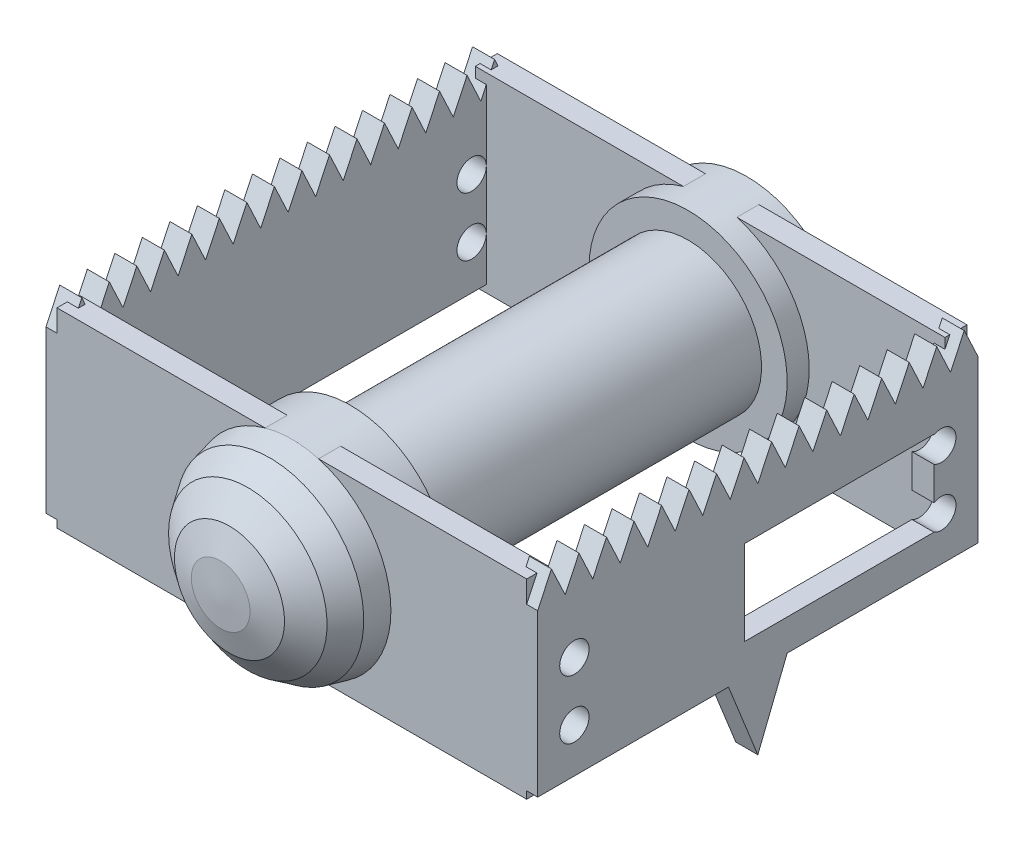
SolidWorks part; units mm, degrees
ref_plane "Alzado" through (0, 0, 0) normal (0, 0, 1) x (1, 0, 0)
ref_plane "Planta" through (0, 0, 0) normal (0, 1, 0) x (1, 0, 0)
ref_plane "Vista lateral" through (0, 0, 0) normal (1, 0, 0) x (0, 0, -1)
sketch "Sk_Eje_cuerpo" plane through (0, 0, 0) normal (0, 1, 0) x (1, 0, 0)
  line L0 (183.5, -84) -> (186, -84)
  line L1 (186, -84) -> (186, -92)
  line L2 (186, -92) -> (182.5, -92)
  line L3 (182.5, -92) -> (182.5, -138)
  line L4 (182.5, -138) -> (186, -138)
  line L5 (186, -138) -> (186, -146)
  line L6 (186, -146) -> (185.3, -149)
  line L7 (185.3, -149) -> (183.3, -152)
  line L8 (183.3, -152) -> (180, -154.5)
  line L9 (180, -154.5) -> (176.5, -155.7)
  line L10 (176.5, -155.7) -> (172.5, -156)
  line L11 (172.5, -156) -> (172.5, -147)
  line L12 (172.5, -147) -> (183.5, -147)
  line L13 (183.5, -147) -> (183.5, -138.5)
  line L14 (183.5, -138.5) -> (178.8, -138.5)
  line L15 (178.8, -138.5) -> (178.8, -91.5)
  line L16 (178.8, -91.5) -> (183.5, -91.5)
  line L17 (183.5, -91.5) -> (183.5, -84)
  line L18 (172.5, -62.1) -> (172.5, -160) construction
revolve "Eje_cuerpo" add sketch "Sk_Eje_cuerpo" angle 360 about L18
sketch "Sk_Placa_delantera" plane through (0, 0, 0) normal (1, 0, 0) x (0, 0, -1)
  line L0 (-86, -12) -> (-112, -12)
  line L1 (-112, -12) -> (-116, -22)
  line L2 (-116, -22) -> (-120, -12)
  line L3 (-120, -12) -> (-146, -12)
  line L4 (-146, -12) -> (-146, 10)
  line L5 (-146, 10) -> (-144.125, 14)
  line L6 (-144.125, 14) -> (-142.25, 10)
  line L7 (-142.25, 10) -> (-140.375, 14)
  line L8 (-140.375, 14) -> (-138.5, 10)
  line L9 (-138.5, 10) -> (-136.625, 14)
  line L10 (-136.625, 14) -> (-134.75, 10)
  line L11 (-134.75, 10) -> (-132.875, 14)
  line L12 (-132.875, 14) -> (-131, 10)
  line L13 (-131, 10) -> (-129.125, 14)
  line L14 (-129.125, 14) -> (-127.25, 10)
  line L15 (-127.25, 10) -> (-125.375, 14)
  line L16 (-125.375, 14) -> (-123.5, 10)
  line L17 (-123.5, 10) -> (-121.625, 14)
  line L18 (-121.625, 14) -> (-119.75, 10)
  line L19 (-119.75, 10) -> (-117.875, 14)
  line L20 (-117.875, 14) -> (-116, 10)
  line L21 (-116, 10) -> (-114.125, 14)
  line L22 (-114.125, 14) -> (-112.25, 10)
  line L23 (-112.25, 10) -> (-110.375, 14)
  line L24 (-110.375, 14) -> (-108.5, 10)
  line L25 (-108.5, 10) -> (-106.625, 14)
  line L26 (-106.625, 14) -> (-104.75, 10)
  line L27 (-104.75, 10) -> (-102.875, 14)
  line L28 (-102.875, 14) -> (-101, 10)
  line L29 (-101, 10) -> (-99.125, 14)
  line L30 (-99.125, 14) -> (-97.25, 10)
  line L31 (-97.25, 10) -> (-95.375, 14)
  line L32 (-95.375, 14) -> (-93.5, 10)
  line L33 (-93.5, 10) -> (-91.625, 14)
  line L34 (-91.625, 14) -> (-89.75, 10)
  line L35 (-89.75, 10) -> (-87.875, 14)
  line L36 (-87.875, 14) -> (-86, 10)
  line L37 (-86, 10) -> (-86, -12)
extrude "Placa_delantera" add sketch "Sk_Placa_delantera" along normal blind 3 from offset 203
sketch3d "Sk_Agujero_Placa_delantera_1"
  line L0 (201.5, -6, 91) -> (207.5, -6, 91)
  dimension "D1" = 6
sweep "Agujero_Placa_delantera_1" cut path "Sk_Agujero_Placa_delantera_1" circular profile diameter 4 parameters "D3"=4
sketch3d "Sk_Agujero_Placa_delantera_2"
  line L0 (201.5, 2, 91) -> (207.5, 2, 91)
  dimension "D1" = 6
sweep "Agujero_Placa_delantera_2" cut path "Sk_Agujero_Placa_delantera_2" circular profile diameter 4 parameters "D3"=4
sketch3d "Sk_Agujero_Placa_delantera_3"
  line L0 (201.5, -6, 141) -> (207.5, -6, 141)
  dimension "D1" = 6
sweep "Agujero_Placa_delantera_3" cut path "Sk_Agujero_Placa_delantera_3" circular profile diameter 4 parameters "D3"=4
sketch3d "Sk_Agujero_Placa_delantera_4"
  line L0 (201.5, 2, 141) -> (207.5, 2, 141)
  dimension "D1" = 6
sweep "Agujero_Placa_delantera_4" cut path "Sk_Agujero_Placa_delantera_4" circular profile diameter 4 parameters "D3"=4
sketch "Sk_Placa_trasera" plane through (0, 0, 0) normal (1, 0, 0) x (0, 0, -1)
  line L0 (-86, -12) -> (-146, -12)
  line L1 (-146, -12) -> (-146, 10)
  line L2 (-146, 10) -> (-144.125, 14)
  line L3 (-144.125, 14) -> (-142.25, 10)
  line L4 (-142.25, 10) -> (-140.375, 14)
  line L5 (-140.375, 14) -> (-138.5, 10)
  line L6 (-138.5, 10) -> (-136.625, 14)
  line L7 (-136.625, 14) -> (-134.75, 10)
  line L8 (-134.75, 10) -> (-132.875, 14)
  line L9 (-132.875, 14) -> (-131, 10)
  line L10 (-131, 10) -> (-129.125, 14)
  line L11 (-129.125, 14) -> (-127.25, 10)
  line L12 (-127.25, 10) -> (-125.375, 14)
  line L13 (-125.375, 14) -> (-123.5, 10)
  line L14 (-123.5, 10) -> (-121.625, 14)
  line L15 (-121.625, 14) -> (-119.75, 10)
  line L16 (-119.75, 10) -> (-117.875, 14)
  line L17 (-117.875, 14) -> (-116, 10)
  line L18 (-116, 10) -> (-114.125, 14)
  line L19 (-114.125, 14) -> (-112.25, 10)
  line L20 (-112.25, 10) -> (-110.375, 14)
  line L21 (-110.375, 14) -> (-108.5, 10)
  line L22 (-108.5, 10) -> (-106.625, 14)
  line L23 (-106.625, 14) -> (-104.75, 10)
  line L24 (-104.75, 10) -> (-102.875, 14)
  line L25 (-102.875, 14) -> (-101, 10)
  line L26 (-101, 10) -> (-99.125, 14)
  line L27 (-99.125, 14) -> (-97.25, 10)
  line L28 (-97.25, 10) -> (-95.375, 14)
  line L29 (-95.375, 14) -> (-93.5, 10)
  line L30 (-93.5, 10) -> (-91.625, 14)
  line L31 (-91.625, 14) -> (-89.75, 10)
  line L32 (-89.75, 10) -> (-87.875, 14)
  line L33 (-87.875, 14) -> (-86, 10)
  line L34 (-86, 10) -> (-86, -12)
extrude "Placa_trasera" add sketch "Sk_Placa_trasera" along normal blind 3 from offset 139
sketch3d "Sk_Agujero_Placa_trasera_1"
  line L0 (137.5, -6, 91) -> (143.5, -6, 91)
  dimension "D1" = 6
sweep "Agujero_Placa_trasera_1" cut path "Sk_Agujero_Placa_trasera_1" circular profile diameter 4 parameters "D3"=4
sketch3d "Sk_Agujero_Placa_trasera_2"
  line L0 (137.5, 2, 91) -> (143.5, 2, 91)
  dimension "D1" = 6
sweep "Agujero_Placa_trasera_2" cut path "Sk_Agujero_Placa_trasera_2" circular profile diameter 4 parameters "D3"=4
sketch3d "Sk_Agujero_Placa_trasera_3"
  line L0 (137.5, -6, 141) -> (143.5, -6, 141)
  dimension "D1" = 6
sweep "Agujero_Placa_trasera_3" cut path "Sk_Agujero_Placa_trasera_3" circular profile diameter 4 parameters "D3"=4
sketch3d "Sk_Agujero_Placa_trasera_4"
  line L0 (137.5, 2, 141) -> (143.5, 2, 141)
  dimension "D1" = 6
sweep "Agujero_Placa_trasera_4" cut path "Sk_Agujero_Placa_trasera_4" circular profile diameter 4 parameters "D3"=4
sketch "Sk_Marco_interior" plane through (0, 0, 0) normal (0, 0, 1) x (1, 0, 0)
  line L0 (140.5, -13) -> (204.5, -13)
  line L1 (204.5, -13) -> (204.5, 13)
  line L2 (204.5, 13) -> (140.5, 13)
  line L3 (140.5, 13) -> (140.5, -13)
  circle A0 centre (172.5, 0) radius 11
  dimension "DIAM1" = 22
extrude "Marco_interior" add sketch "Sk_Marco_interior" along normal blind 3 from offset 86
sketch "Sk_Marco_exterior" plane through (0, 0, 0) normal (0, 0, 1) x (1, 0, 0)
  line L0 (140.5, -13) -> (204.5, -13)
  line L1 (204.5, -13) -> (204.5, 13)
  line L2 (204.5, 13) -> (140.5, 13)
  line L3 (140.5, 13) -> (140.5, -13)
  circle A0 centre (172.5, 0) radius 11
  dimension "DIAM2" = 22
extrude "Marco_exterior" add sketch "Sk_Marco_exterior" along normal blind 3 from offset 143
ref_axis "Eje_pedal" through (172.5, 0, 146) along (0, 0, -1)
sketch "Croquis17" plane through (206, 0, 0) normal (1, 0, 0) x (0, 0, -1)
  line L0 (-92, 3.8293) -> (-117.7956, 3.8293)
  line L1 (-92, 10) -> (-92, -10) construction
  line L2 (-92, 13.5) -> (-92, -13.5) construction
  line L3 (-117.7956, 3.8293) -> (-117.7956, -7.7321)
  line L4 (-117.7956, -7.7321) -> (-92, -7.7321)
  line L5 (-92, -7.7321) -> (-92, 3.8293)
  circle A0 centre (-91, -6) radius 2 construction
extrude "Cortar-Extruir1" cut sketch "Croquis17" against normal blind 10
